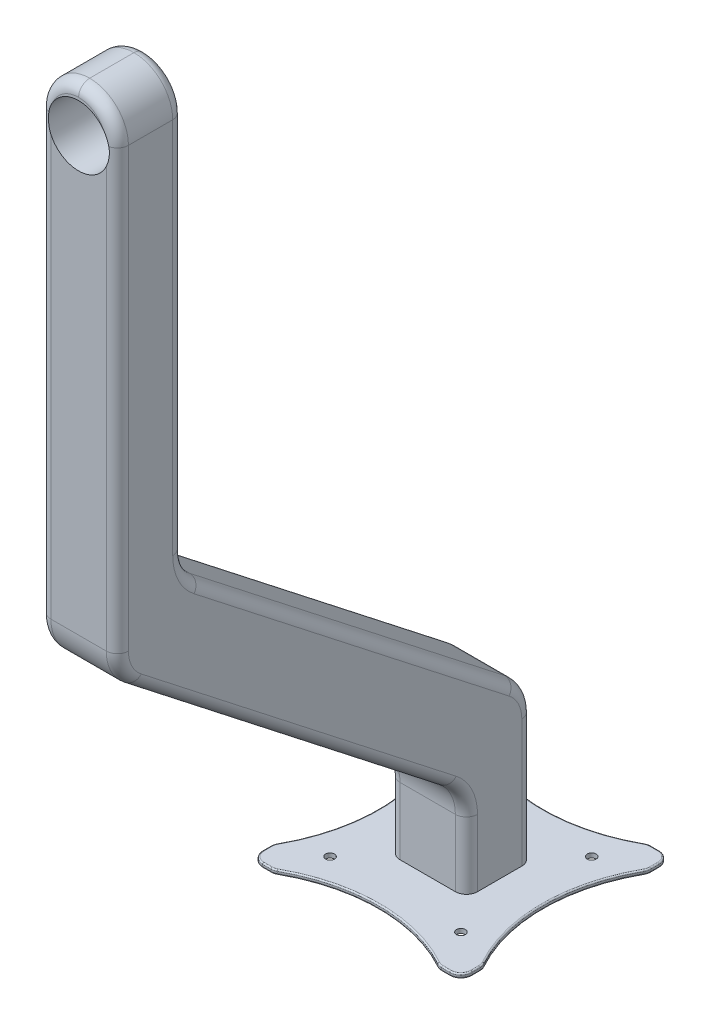
SolidWorks part; units mm, degrees
material "1060 Alloy"
ref_plane "Front" through (0, 0, 0) normal (0, 0, 1) x (1, 0, 0)
ref_plane "Top" through (0, 0, 0) normal (0, 1, 0) x (1, 0, 0)
ref_plane "Right" through (0, 0, 0) normal (1, 0, 0) x (0, 0, -1)
sketch "Sketch1" plane through (0, 0, 0) normal (0, 1, 0) x (1, 0, 0)
  line L0 (0, 47.3) -> (0, 0) construction
  line L1 (-60, 60) -> (-47.3, 60)
  line L2 (-60, 60) -> (-60, 47.3)
  line L3 (-60, -60) -> (-47.3, -60)
  line L4 (60, 60) -> (60, 47.3)
  line L5 (-60, 60) -> (60, -60) construction
  line L6 (-60, -60) -> (60, 60) construction
  line L7 (47.3, -60) -> (60, -60)
  line L8 (-37.5, 37.5) -> (37.5, 37.5) construction
  line L9 (-37.5, 37.5) -> (-37.5, -37.5) construction
  line L10 (-37.5, -37.5) -> (37.5, -37.5) construction
  line L11 (37.5, 37.5) -> (37.5, -37.5) construction
  line L12 (-37.5, 37.5) -> (37.5, -37.5) construction
  line L13 (-37.5, -37.5) -> (37.5, 37.5) construction
  line L14 (60, -47.3) -> (60, -60)
  line L15 (47.3, 60) -> (60, 60)
  line L16 (-60, -47.3) -> (-60, -60)
  arc A0 (-47.3, 60) -> (47.3, 60) centre (0, 141.7323) ccw
  circle A1 centre (-37.5, 37.5) radius 2.5527
  circle A2 centre (-37.5, -37.5) radius 2.5527
  circle A3 centre (37.5, -37.5) radius 2.5527
  circle A4 centre (37.5, 37.5) radius 2.5527
  arc A5 (60, 47.3) -> (60, -47.3) centre (141.7323, 0) ccw
  arc A6 (47.3, -60) -> (-47.3, -60) centre (0, -141.7323) ccw
  arc A7 (-60, -47.3) -> (-60, 47.3) centre (-141.7323, 0) ccw
  point P0 (0, 0)
  point P31 (0, 0)
  dimension "D3" = 5.1054
  dimension "D7" = 12.7
  dimension "D1" = 120
  dimension "D4" = 75
  dimension "D5" = 75
  dimension "D6" = 12.7
  dimension "D8" = 4
extrude "Boss-Extrude1" add sketch "Sketch1" along normal blind 2.54
fillet "Fillet1" radius 6.35 12 edges at (-60, 1.27, -47.3) (-60, 1.27, -60) (-47.3, 1.27, -60) (47.3, 1.27, -60) (60, 1.27, -60) (60, 1.27, -47.3) (60, 1.27, 47.3) (60, 1.27, 60) (47.3, 1.27, 60) (-47.3, 1.27, 60) (-60, 1.27, 60) (-60, 1.27, 47.3)
sketch "Sketch3" plane through (0, 0, 0) normal (1, 0, 0) x (0, 0, -1)
  line L0 (0, 2.54) -> (0, 70.6896) construction
  line L1 (45.8895, 2.54) -> (-45.8895, 2.54) construction
  line L2 (0, 70.6896) -> (-200.1547, 227.0676) construction
  line L3 (-200.1547, 227.0676) -> (-200.1547, 495.4608) construction
  line L4 (19.05, 2.54) -> (19.05, 88.0391)
  line L5 (-19.05, 2.54) -> (-19.05, 53.34)
  line L6 (19.05, 88.0391) -> (-181.1047, 244.4172)
  line L7 (-19.05, 53.34) -> (-219.2047, 209.718)
  line L8 (-181.1047, 244.4172) -> (-181.1047, 495.4608)
  line L9 (-219.2047, 209.718) -> (-219.2047, 495.4608)
  line L10 (-219.2047, 227.0676) -> (-219.2047, 495.4608) construction
  line L11 (19.05, 2.54) -> (19.05, 70.6896) construction
  line L12 (15.6378, 90.705) -> (-184.5169, 247.0831) construction
  line L13 (-19.05, 2.54) -> (-19.05, 70.6896) construction
  line L14 (-15.6378, 50.6741) -> (-215.7925, 207.0521) construction
  line L15 (-181.1047, 227.0676) -> (-181.1047, 495.4608) construction
  line L16 (-181.1047, 495.4608) -> (-219.2047, 495.4608)
  line L17 (19.05, 2.54) -> (-19.05, 2.54)
  dimension "D8" = 254
  dimension "D9" = 128
  dimension "D10" = 50.8
  dimension "D11" = 251.0436
  dimension "D2" = 19.05
  dimension "D3" = 19.05
  dimension "D4" = 25.4
  dimension "D5" = 25.4
  dimension "D6" = 19.05
  dimension "D7" = 19.05
extrude "Boss-Extrude2" add sketch "Sketch3" along normal mid plane 44.45 separate body
sketch "Sketch4" plane through (0, 0, 181.1047) normal (0, 0, -1) x (-1, 0, 0)
  line L0 (0, 495.4608) -> (0, 470.0608) construction
  line L1 (-22.225, 495.4608) -> (22.225, 495.4608) construction
  circle A0 centre (0, 470.0608) radius 17.4625
  dimension "D1" = 34.925
  dimension "D2" = 25.4
extrude "Cut-Extrude1" cut sketch "Sketch4" against normal through all
fillet "Fillet2" radius 22.225 2 edges at (-22.225, 495.4608, 200.1547) (22.225, 495.4608, 200.1547)
fillet "Fillet3" radius 25.4 4 edges at (0, 53.34, 19.05) (0, 88.0391, -19.05) (0, 244.4172, 181.1047) (0, 209.718, 219.2047)
fillet "Fillet4" radius 6.35 24 edges at (-22.225, 21.7458, 19.05) (-22.225, 52.0862, 21.6206) (-22.225, 131.529, 119.1274) (-22.225, 210.9718, 216.6341) (-22.225, 347.6711, 219.2047) (-15.7154, 488.9512, 219.2047) (15.7154, 488.9512, 219.2047) (22.225, 21.7458, 19.05) (22.225, 52.0862, 21.6206) (22.225, 131.529, 119.1274) (22.225, 210.9718, 216.6341) (22.225, 39.0954, -19.05) (22.225, 86.7854, -16.4794) (22.225, 166.2282, 81.0274) (22.225, 245.6709, 178.5341) (-22.225, 39.0954, -19.05) (-22.225, 86.7854, -16.4794) (-22.225, 166.2282, 81.0274) (-22.225, 245.6709, 178.5341) (-22.225, 365.0207, 181.1047) (-15.7154, 488.9512, 181.1047) (15.7154, 488.9512, 181.1047) (22.225, 347.6711, 219.2047) (22.225, 365.0207, 181.1047)
fillet "Fillet5" radius 0.762 48 edges at (47.3814, 2.54, -59.7967) (51.3126, 2.54, -60) (58.1401, 2.54, -58.1401) (60, 2.54, -51.3126) (59.7967, 2.54, -47.3814) (47.3, 2.54, 0) (59.7967, 2.54, 47.3814) (60, 2.54, 51.3126) (58.1401, 2.54, 58.1401) (51.3126, 2.54, 60) (47.3814, 2.54, 59.7967) (0, 2.54, 47.3) (-47.3814, 2.54, 59.7967) (-51.3126, 2.54, 60) (-58.1401, 2.54, 58.1401) (-60, 2.54, 51.3126) (-59.7967, 2.54, 47.3814) (-47.3, 2.54, 0) (-59.7967, 2.54, -47.3814) (-60, 2.54, -51.3126) (-58.1401, 2.54, -58.1401) (-51.3126, 2.54, -60) (-47.3814, 2.54, -59.7967) (47.3814, 0, -59.7967) (51.3126, 0, -60) (58.1401, 0, -58.1401) (60, 0, -51.3126) (59.7967, 0, -47.3814) (47.3, 0, 0) (59.7967, 0, 47.3814) (60, 0, 51.3126) (58.1401, 0, 58.1401) (51.3126, 0, 60) (47.3814, 0, 59.7967) (0, 0, 47.3) (-47.3814, 0, 59.7967) (-51.3126, 0, 60) (-58.1401, 0, 58.1401) (-60, 0, 51.3126) (-59.7967, 0, 47.3814) (-47.3, 0, 0) (-59.7967, 0, -47.3814) (-60, 0, -51.3126) (-58.1401, 0, -58.1401) (-51.3126, 0, -60) (-47.3814, 0, -59.7967) (0, 2.54, -47.3) (0, 0, -47.3)
